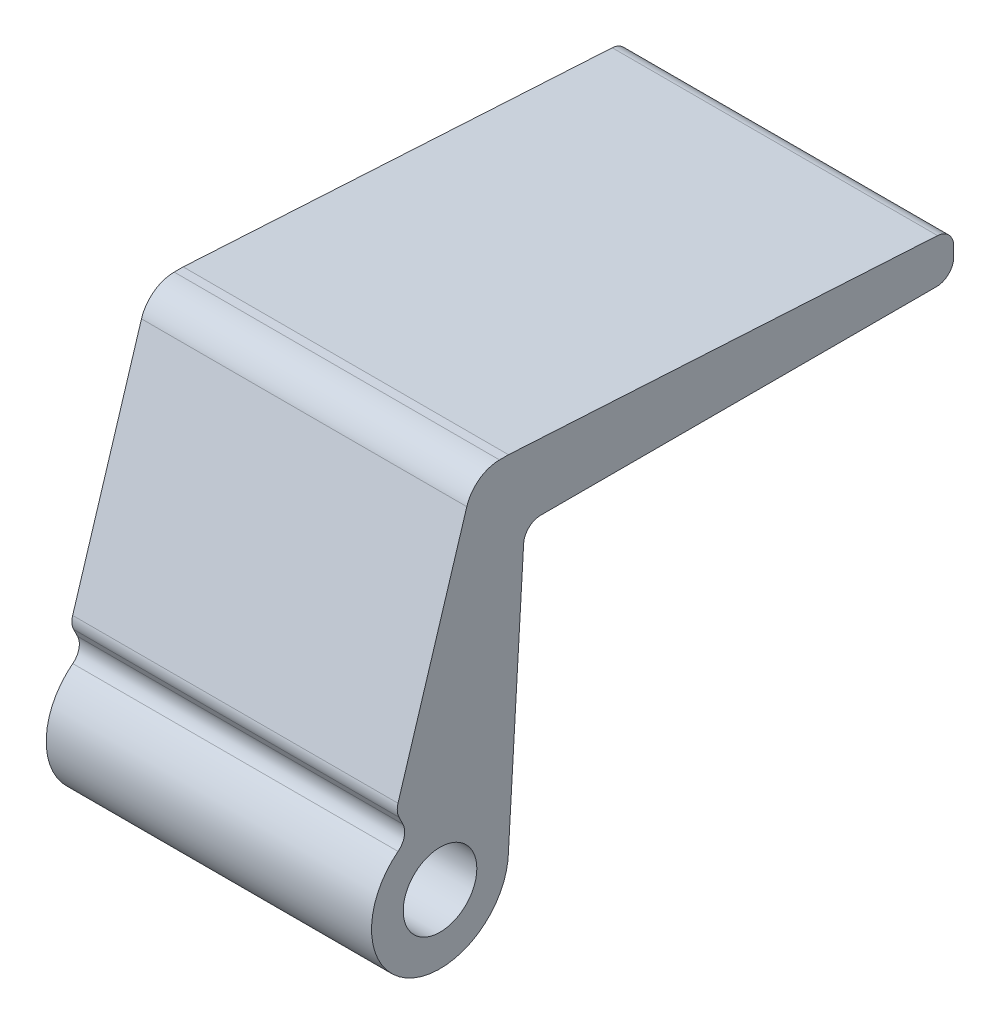
SolidWorks part; units mm, degrees
ref_plane "Front Plane" through (0, 0, 0) normal (0, 0, 1) x (1, 0, 0)
ref_plane "Top Plane" through (0, 0, 0) normal (0, 1, 0) x (1, 0, 0)
ref_plane "Right Plane" through (0, 0, 0) normal (1, 0, 0) x (0, 0, -1)
sketch "Sketch1" plane through (0, 0, 0) normal (1, 0, 0) x (0, 0, -1)
  line L28 (30, 18.5) -> (30, 17)
  line L29 (2, 20) -> (4, 20)
  line L30 (2, 20) -> (-2.5722, 5.2199)
  line L32 (4, 20) -> (30, 18.5)
  line L33 (30, 17) -> (30, 16)
  line L34 (-2.5722, 5.2199) -> (-1.7681, 3.588)
  line L35 (4.9388, 16) -> (4, 0)
  line L36 (30, 16) -> (4.9388, 16)
  circle A5 centre (0, 0) radius 2.15
  arc A8 (-1.7681, 3.588) -> (4, 0) centre (0, 0) ccw
extrude "Boss-Extrude1" add sketch "Sketch1" along normal mid plane 19
fillet "Fillet1" radius 2 1 edges at (0, 20, -2)
fillet "Fillet2" radius 1 5 edges at (0, 18.5, -30) (0, 16, -30) (0, 16, -4.9388) (0, 3.588, 1.7681) (0, 5.2199, 2.5722)
